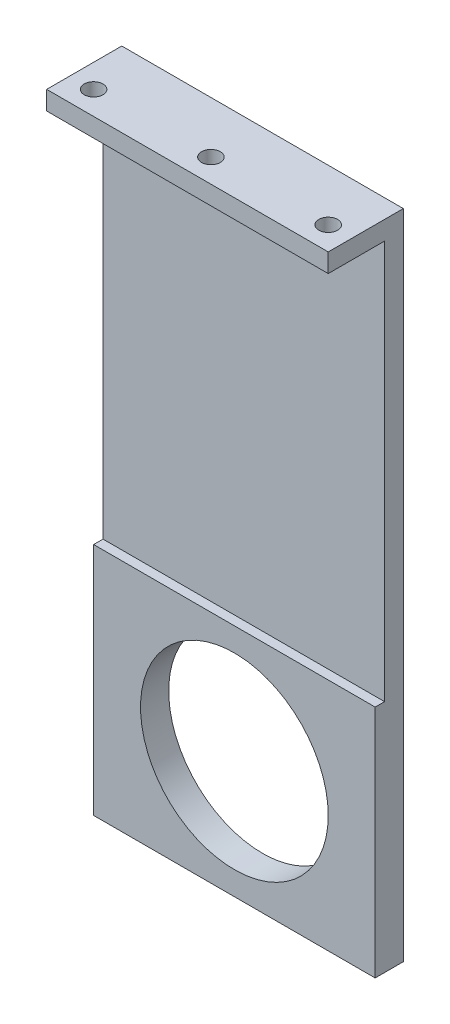
SolidWorks part; units mm, degrees
ref_plane "Front Plane" through (0, 0, 0) normal (0, 0, 1) x (1, 0, 0)
ref_plane "Top Plane" through (0, 0, 0) normal (0, 1, 0) x (1, 0, 0)
ref_plane "Right Plane" through (0, 0, 0) normal (1, 0, 0) x (0, 0, -1)
sketch "Sketch1" plane through (0, 0, 0) normal (0, 0, 1) x (1, 0, 0)
  line L5 (30, -25) -> (-30, -25)
  line L6 (30, -25) -> (30, 25)
  line L7 (30, 25) -> (-30, 25)
  line L8 (-30, -25) -> (-30, 25)
  line L9 (30, -25) -> (-30, 25) construction
  line L10 (30, 25) -> (-30, -25) construction
  line L11 (-30, 25) -> (30, 25)
  line L12 (-30, 25) -> (-30, 110)
  line L13 (-30, 110) -> (30, 110)
  line L14 (30, 25) -> (30, 110)
  circle A0 centre (0, 0) radius 20
  dimension "D1" = 40
  dimension "D2" = 60
  dimension "D3" = 50
  dimension "D4" = 110
extrude "Boss-Extrude1" add sketch "Sketch1" along normal blind 6 contours L8 L5 L6 L7 A0 region at (0, -24.219, 0)
extrude "Boss-Extrude2" add sketch "Sketch1<3>" along normal blind 4 contours L7 L14 L13 L12 region at (0, 67.5, 0)
sketch "Sketch1<3>" plane through (0, 0, 0) normal (0, 0, 1) x (1, 0, 0) same geometry as "Sketch1"
sketch "Sketch4" plane through (0, 110, 0) normal (0, 1, 0) x (1, 0, 0)
  line L1 (-30, 0) -> (30, 0)
  line L2 (-30, 0) -> (-30, -16)
  line L3 (-30, -16) -> (30, -16)
  line L4 (30, 0) -> (30, -16)
  circle A0 centre (-25, -11) radius 2
  circle A1 centre (0, -11) radius 2
  circle A2 centre (25, -11) radius 2
  point P11 (0, 0)
  point P13 (0, 0)
  point P15 (0, 0)
  dimension "D2" = 4
  dimension "D1" = 16
  dimension "D3" = 25
  dimension "D4" = 5
  dimension "D5" = 25
extrude "Boss-Extrude3" add sketch "Sketch4" along normal blind 4
